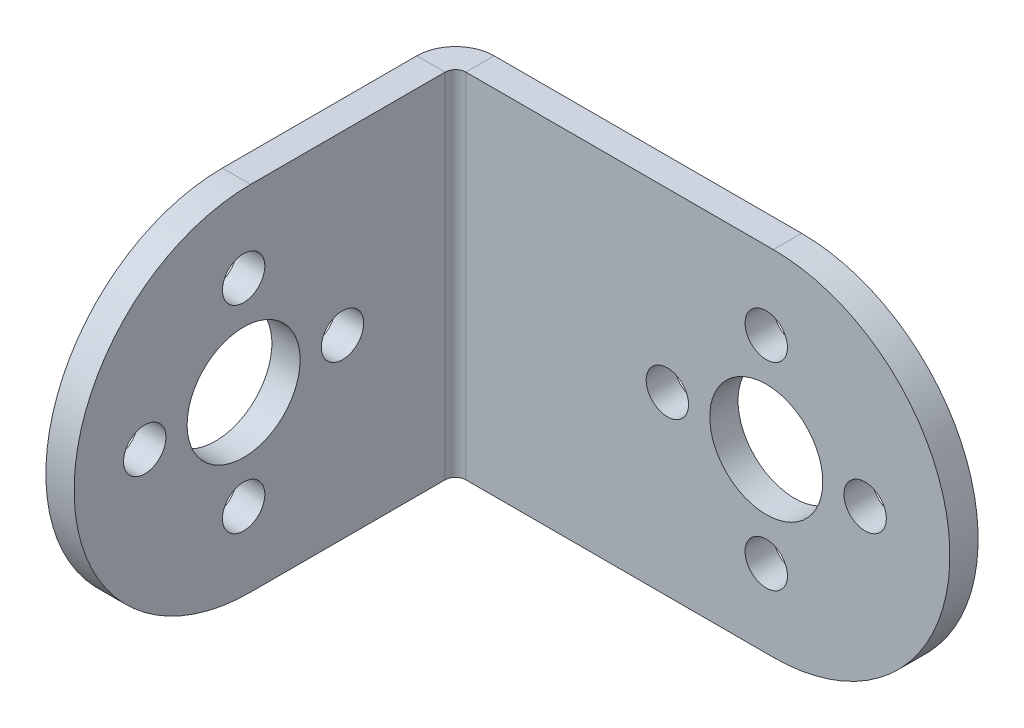
SolidWorks part; units mm, degrees
note: The reader was unsure of these and kept them because the rebuilt part matched: flange length of "边线-法兰1".
material "普通碳钢"
ref_plane "前视" through (0, 0, 0) normal (0, 0, 1) x (1, 0, 0)
ref_plane "上视" through (0, 0, 0) normal (0, 1, 0) x (1, 0, 0)
ref_plane "右视" through (0, 0, 0) normal (1, 0, 0) x (0, 0, -1)
sketch "草图1" plane through (0, 0, 0) normal (0, 0, 1) x (1, 0, 0)
  line L0 (0, 0) -> (0, -25)
  line L1 (0, -25) -> (24.5, -25)
  line L2 (0, 0) -> (24.5, 0)
  line L3 (0, -12.5) -> (37, -12.5) construction
  line L4 (24, -5.5) -> (24, -19.5) construction
  arc A0 (24.5, 0) -> (24.5, -25) centre (24.5, -12.5) cw
  circle A1 centre (24, -12.5) radius 4
  circle A2 centre (17, -12.5) radius 1.5
  circle A3 centre (31, -12.5) radius 1.5
  circle A4 centre (24, -19.5) radius 1.5
  circle A5 centre (24, -5.5) radius 1.5
  circle A6 centre (24, -12.5) radius 7 construction
  dimension "D3" = 8
  dimension "D4" = 3
  dimension "D5" = 14
  dimension "D1" = 25
  dimension "D2" = 37
  dimension "24" = 24
base flange "基体-法兰1" sketch "草图1" thickness 2 reverse thickness direction no parameters "D1"=0.7366
edge flange "边线-法兰1" sketch "草图8" flange angle 90 flange length 30 flange position material inside bend radius 0.7366 thickness 2 relief rectangular parameters "D6"=0
sketch "草图8" plane through (0, 0, 0) normal (1, 0, 0) x (0, 1, 0)
  line L1 (0, 0) -> (-25, 0) construction
  line L2 (-25, 0) -> (-25, 28)
  line L3 (-25, 28) -> (0, 28)
  line L4 (0, 28) -> (0, 0)
  line L5 (0, 0) -> (-25, 0)
bend "边线折弯1" bend radius 0.7366 bend angle 90 parameters "D5"=1
sketch "草图9" plane through (0, 0, 0) normal (-1, 0, 0) x (0, 0, 1)
  line L0 (28, -12.5) -> (-2, -12.5) construction
  line L1 (28, 0) -> (28, -25) construction
  line L2 (-2, -25) -> (-2, 0) construction
  line L3 (15, -5.5) -> (15, -19.5) construction
  line L4 (0.7366, 0) -> (28, 0) construction
  line L5 (28, -25) -> (0.7366, -25) construction
  line L6 (14.5, 0) -> (28, 0)
  line L7 (28, 0) -> (28, -25)
  line L8 (28, -25) -> (14.5, -25)
  circle A0 centre (15, -12.5) radius 4
  circle A1 centre (22, -12.5) radius 1.5
  circle A2 centre (8, -12.5) radius 1.5
  circle A3 centre (15, -19.5) radius 1.5
  circle A4 centre (15, -5.5) radius 1.5
  circle A5 centre (15, -12.5) radius 7 construction
  arc A6 (14.5, 0) -> (14.5, -25) centre (14.5, -12.5) cw
  dimension "D1" = 8
  dimension "D2" = 17
  dimension "D3" = 14
  dimension "D4" = 3
  dimension "D5" = 12.5
  dimension "D6" = 29
extrude "切除-拉伸1" cut sketch "草图9" against normal blind 10 normal cut yes
sketch "折弯-线1" plane through (0, 0, 0) normal (0, 1, 0) x (1, 0, 0)
sketch "边界框1" plane through (0, 0, 0) normal (0, 1, 0) x (1, 0, 0)
sheet metal parameters "钣金4" thickness 2 parameters "D1"=0.7366
flat pattern "平板型式4" [suppressed]
sketch "折弯-线2" plane through (0, 0, 0) normal (0, 1, 0) x (1, 0, 0)
sketch "边界框2" [suppressed] plane through (0, 0, 0) normal (0, 1, 0) x (1, 0, 0)
sheet metal parameters "钣金5" thickness 2 parameters "D1"=0.7366
flat pattern "平板型式4" [suppressed]
sketch "折弯-线2" plane through (0, 0, 0) normal (0, 1, 0) x (1, 0, 0)
sketch "边界框2" [suppressed] plane through (0, 0, 0) normal (0, 1, 0) x (1, 0, 0)
bend of the flat pattern "展开-<边线折弯1>1"
sheet metal parameters "钣金6" thickness 2 parameters "D1"=0.7366
flat pattern "平板型式4"
sketch "折弯-线2" plane through (0, 0, 0) normal (0, 0, 1) x (1, 0, 0)
  line L0 (1.3727, 0) -> (1.3727, -25) construction
  line L1 (1.3727, 0) -> (1.3727, -25) construction
sketch3d "边界框2" [suppressed]
  line L0 (-50.7546, -12.5, 0) -> (12.5, -12.5, 0) construction
  line L1 (-50.7546, 12.5, 0) -> (12.5, 12.5, 0) construction
  line L2 (-50.7546, -12.5, 0) -> (-50.7546, 12.5, 0) construction
  line L3 (12.5, -12.5, 0) -> (12.5, 12.5, 0) construction
bend of the flat pattern "展开-<边线折弯1>1"
